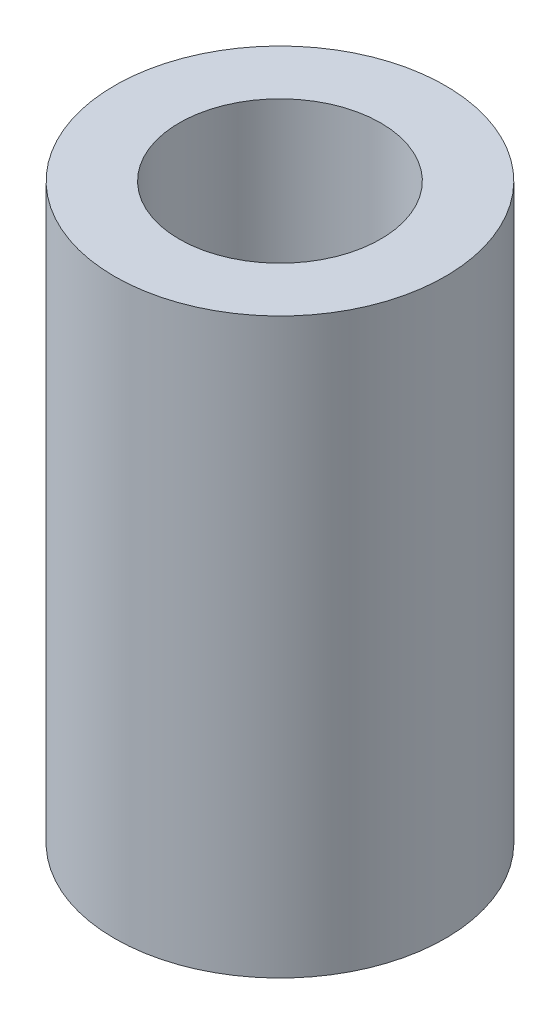
SolidWorks part; units mm, degrees
material "Amonium Percholorate"
ref_plane "Front Plane" through (0, 0, 0) normal (0, 0, 1) x (1, 0, 0)
ref_plane "Top Plane" through (0, 0, 0) normal (0, 1, 0) x (1, 0, 0)
ref_plane "Right Plane" through (0, 0, 0) normal (1, 0, 0) x (0, 0, -1)
sketch "Sketch2" plane through (0, 0, 0) normal (0, 1, 0) x (1, 0, 0)
  circle A0 centre (0, 0) radius 44.831
  circle A1 centre (0, 0) radius 27.305
  dimension "D1" = 89.662
  dimension "D2" = 54.61
extrude "Extrude1" add sketch "Sketch2" along normal blind 155.4378
